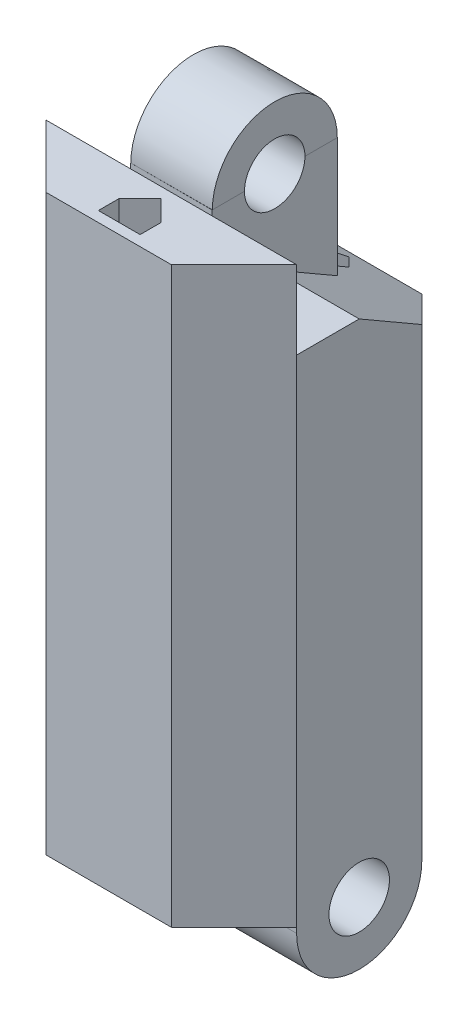
SolidWorks part; units mm, degrees
ref_plane "Front Plane" through (0, 0, 0) normal (0, 0, 1) x (1, 0, 0)
ref_plane "Top Plane" through (0, 0, 0) normal (0, 1, 0) x (1, 0, 0)
ref_plane "Right Plane" through (0, 0, 0) normal (1, 0, 0) x (0, 0, -1)
sketch "Sketch2" plane through (0, 0, 0) normal (0, 1, 0) x (1, 0, 0)
  line L0 (-3, 6) -> (3, 6)
  line L1 (3, 6) -> (6, 3)
  line L2 (6, 3) -> (6, -3)
  line L3 (6, -3) -> (3, -6)
  line L4 (3, -6) -> (-3, -6)
  line L5 (-3, -6) -> (-6, -3)
  line L6 (-6, -3) -> (-6, 3)
  line L7 (-6, 3) -> (-3, 6)
  point P2 (0, -6)
  point P9 (0, 6)
  point P12 (-6, 0)
  point P13 (6, 0)
  dimension "D1" = 12
  dimension "D2" = 12
  dimension "D3" = 6
  dimension "D4" = 6
  dimension "D5" = 6
extrude "Boss-Extrude1" add sketch "Sketch2" along normal mid plane 20 contours L7 L0 L1 L2 L3 L4 L5 L6
sketch "Sketch5" plane through (0, 0, 0) normal (1, 0, 0) x (0, 0, -1)
  line L1 (3, 10) -> (-3, 10) construction
  line L2 (0, 10) -> (6, 6.5359)
  line L3 (6, 10) -> (6, -10) construction
  line L4 (6, 6.5359) -> (6, 10)
  line L5 (6, 10) -> (0, 10)
  dimension "D1" = 30
extrude "Cut-Extrude2" cut sketch "Sketch5" against normal through all both and the other way through all
mirror "Mirror3" about plane through (0, 0, 0) normal (0, 1, 0) of "Cut-Extrude2"
sketch "Sketch6" plane through (0, -10, 0) normal (0, -1, 0) x (1, 0, 0)
  line L1 (-6, 3) -> (-2.1, 3)
  line L2 (-6, 3) -> (-6, -3)
  line L3 (-6, -3) -> (-2.1, -3)
  line L4 (-2.1, 3) -> (-2.1, -3)
  dimension "D1" = 3.9
extrude "Boss-Extrude3" add sketch "Sketch6" along normal mid plane 8
sketch "Sketch7" plane through (0, -14, 0) normal (0, -1, 0) x (1, 0, 0)
  line L0 (-6, 3) -> (-6, -3) construction
  line L1 (-6, 0) -> (-2.1, 0)
  line L2 (-6, 0) -> (-6, 3)
  line L3 (-6, 3) -> (-2.1, 3)
  line L4 (-2.1, 0) -> (-2.1, 3)
revolve "Revolve1" add sketch "Sketch7" angle 180 about L1
sketch "Sketch8" plane through (-6, 0, 0) normal (-1, 0, 0) x (0, 0, 1)
  line L0 (-3, -14) -> (3, -14) construction
sketch "Sketch9" plane through (-6, 0, 0) normal (-1, 0, 0) x (0, 0, 1)
  line L0 (-3, -14) -> (3, -14) construction
  circle A0 centre (0, -14) radius 1.45
  dimension "D1" = 2.9
extrude "Cut-Extrude3" cut sketch "Sketch9" against normal mid plane 10
mirror "Mirror5" about plane through (0, 0, 0) normal (1, 0, 0) of "Revolve1", "Boss-Extrude3", "Cut-Extrude3"
sketch "Sketch10" plane through (0, 10, 0) normal (0, 1, 0) x (1, 0, 0)
  line L0 (-6, -3) -> (6, -3) construction
  line L1 (-1.95, -3) -> (1.95, -3)
  line L2 (-1.95, -3) -> (-1.95, 3)
  line L3 (-1.95, 3) -> (1.95, 3)
  line L4 (1.95, -3) -> (1.95, 3)
  line L5 (-1.95, -3) -> (1.95, 3) construction
  line L6 (-1.95, 3) -> (1.95, -3) construction
  point P6 (0, 0)
  dimension "D1" = 3.9
extrude "Boss-Extrude4" add sketch "Sketch10" along normal mid plane 8
sketch "Sketch12" plane through (0, 14, 0) normal (0, 1, 0) x (1, 0, 0)
  line L0 (-1.95, 3) -> (-1.95, 0)
  line L3 (-1.95, 3) -> (1.95, 3)
  line L4 (1.95, 0.0037) -> (1.95, 3)
  line L5 (-1.95, 3) -> (-1.95, -3) construction
  line L6 (-1.95, 0) -> (1.95, 0.0037)
revolve "Revolve2" add sketch "Sketch12" angle 180 about L6
sketch "Sketch13" plane through (-1.95, 0, 0) normal (-1, 0, 0) x (0, 0, 1)
  line L0 (-3, 14) -> (3, 14) construction
  line L1 (0, 14) -> (3, 14) construction
  point P4 (0, 0)
  point P5 (2.8635, 14)
  point P8 (3, 14)
sketch "Sketch14" plane through (-1.95, 0, 0) normal (-1, 0, 0) x (0, 0, 1)
  line L0 (-3, 14) -> (3, 14) construction
  circle A0 centre (0, 14) radius 1.45
  dimension "D1" = 2.9
extrude "Cut-Extrude4" cut sketch "Sketch14" against normal mid plane 10
sketch "Sketch17" plane through (0, 10, 0) normal (0, 1, 0) x (1, 0, 0)
  line L0 (-6, -3) -> (-1.95, -3)
  line L1 (-1.95, -3) -> (1.95, -3)
  line L2 (6, -3) -> (1.95, -3)
  line L3 (3, -6) -> (6, -3)
  line L4 (-6, -3) -> (-3, -6)
  line L5 (-3, -6) -> (3, -6)
extrude "Boss-Extrude7" add sketch "Sketch17" along normal blind 3.75
sketch "Sketch15" plane through (0, 0, 0) normal (0, 1, 0) x (1, 0, 0)
  line L0 (0, 5.5) -> (-1, 4.5)
  line L1 (-1, 4.5) -> (-1, 3.5)
  line L2 (-1, 3.5) -> (1, 3.5)
  line L3 (1, 3.5) -> (1, 4.5)
  line L4 (1, 4.5) -> (0, 5.5)
  line L6 (1, -4.5) -> (0, -3.5)
  line L7 (0, -3.5) -> (-1, -4.5)
  line L8 (-1, -4.5) -> (-1, -5.5)
  line L9 (-1, -5.5) -> (1, -5.5)
  line L10 (1, -5.5) -> (1, -4.5)
  line L12 (1.95, -3) -> (-1.95, -3) construction
  line L13 (1.95, 3) -> (-1.95, 3) construction
  dimension "D1" = 2
  dimension "D2" = 2
  dimension "D3" = 135
  dimension "D4" = 135
  dimension "D5" = 1
  dimension "D6" = 2
  dimension "D7" = 0.5
  dimension "D8" = 0.5
sketch "Sketch19" plane through (0, -10, 0) normal (0, -1, 0) x (1, 0, 0)
  line L0 (-6, 3) -> (-2.1, 3)
  line L1 (-2.1, 3) -> (2.1, 3)
  line L2 (2.1, 3) -> (6, 3)
  line L3 (6, 3) -> (3, 6)
  line L4 (3, 6) -> (-3, 6)
  line L5 (-3, 6) -> (-6, 3)
extrude "Boss-Extrude17" add sketch "Sketch19" along normal blind 3.75
extrude "Cut-Extrude6" cut sketch "Sketch15" against normal through all both and the other way through all
